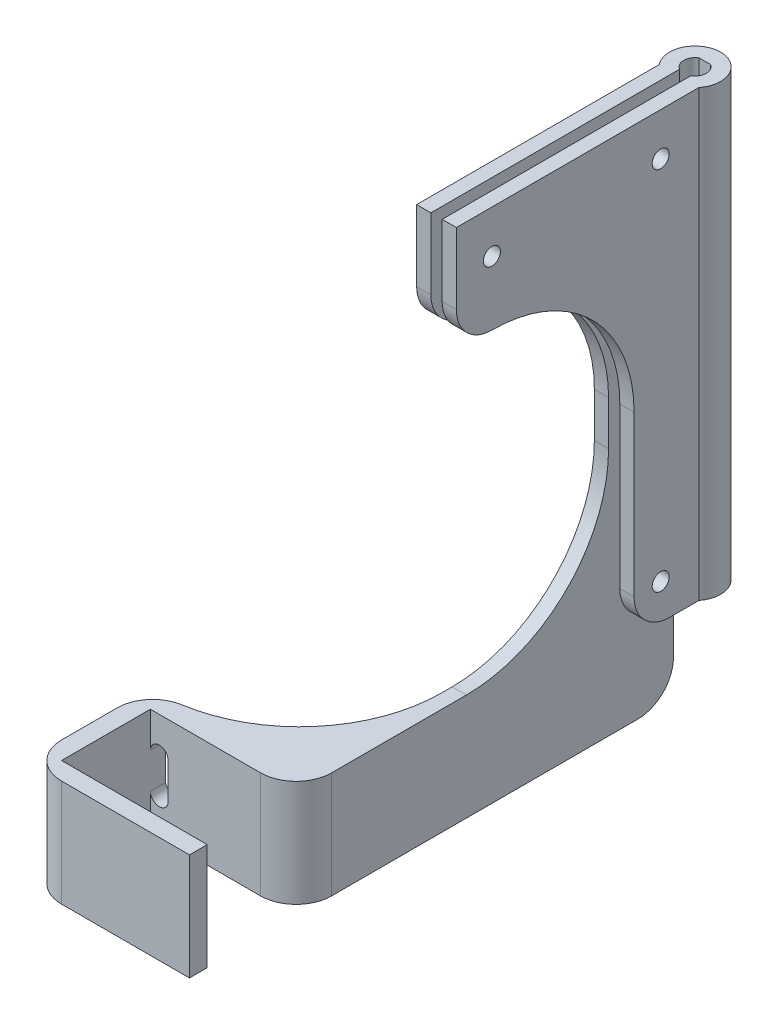
SolidWorks part; units mm, degrees
ref_plane "Front Plane" through (0, 0, 0) normal (0, 0, 1) x (1, 0, 0)
ref_plane "Top Plane" through (0, 0, 0) normal (0, 1, 0) x (1, 0, 0)
ref_plane "Right Plane" through (0, 0, 0) normal (1, 0, 0) x (0, 0, -1)
sketch "Sketch1" plane through (0, 0, 0) normal (0, 1, 0) x (1, 0, 0)
  line L0 (-1.5875, -2.7496) -> (-1.5875, -22.7496)
  line L1 (1.5875, -2.7496) -> (1.5875, -22.7496)
  line L2 (1.5875, 2.7496) -> (-1.5875, 2.7496)
  line L3 (5.5875, -4.5012) -> (5.5875, -22.7496)
  line L4 (-5.5875, -4.5012) -> (-5.5875, -22.7496)
  line L5 (-5.5875, -22.7496) -> (-1.5875, -22.7496)
  line L6 (1.5875, -22.7496) -> (5.5875, -22.7496)
  arc A0 (1.5875, -2.7496) -> (1.5875, 2.7496) centre (0, 0) ccw
  arc A1 (5.5875, -4.5012) -> (-5.5875, -4.5012) centre (0, 0) ccw
  arc A2 (-1.5875, 2.7496) -> (-1.5875, -2.7496) centre (0, 0) ccw
  arc A4 (1.5875, -2.7496) -> (-1.5875, -2.7496) centre (0, 0) ccw construction
  dimension "D1" = 3.175
  dimension "D2" = 20
  dimension "D3" = 3.175
  dimension "D5" = 3.175
  dimension "D4" = 4
extrude "Boss-Extrude1" add sketch "Sketch1" along normal blind 125
sketch "Sketch5" plane through (0, 125, 0) normal (0, 1, 0) x (1, 0, 0)
  line L1 (-1.5875, -110.675) -> (-1.5875, -105.675)
  line L2 (-47.5875, -105.675) -> (-47.5875, -140.675)
  line L3 (-47.5875, -140.675) -> (-1.5875, -140.675)
  line L4 (-1.5875, -140.675) -> (-1.5875, -135.675)
  line L5 (-1.5875, -135.675) -> (-42.5875, -135.675)
  line L9 (-1.5875, -22.7496) -> (-1.5875, -2.7496) construction
  line L10 (-42.5875, -110.675) -> (-1.5875, -110.675)
  line L12 (-42.5875, -135.675) -> (-42.5875, -110.675)
  line L13 (-47.5875, -105.675) -> (-1.5875, -105.675)
  line L18 (-18.6703, -3.175) -> (17.7565, -3.175) construction
  circle A0 centre (0, 0) radius 3.175 construction
  arc A1 (-1.5875, 2.7496) -> (-1.5875, -2.7496) centre (0, 0) ccw construction
  point P2 (-42.5875, -123.175)
  dimension "D2" = 120
  dimension "D1" = 41
  dimension "D3" = 25
  dimension "D4" = 5
  dimension "D5" = 5
  dimension "D7" = 5
extrude "Boss-Extrude2" add sketch "Sketch5" against normal mid plane 30 from offset 137.5 offset against normal yes
sketch "Sketch6" plane through (0, 125, 0) normal (0, 1, 0) x (1, 0, 0)
  line L0 (5.5875, -22.7496) -> (5.5875, -4.5012) construction
  line L1 (1.5875, -22.7496) -> (5.5875, -22.7496)
  line L2 (1.5875, -22.7496) -> (1.5875, -72.7496)
  line L3 (1.5875, -72.7496) -> (5.5875, -72.7496)
  line L4 (5.5875, -22.7496) -> (5.5875, -72.7496)
  line L6 (-1.5875, -22.7496) -> (-1.5875, -2.7496) construction
  line L7 (-5.5875, -22.7496) -> (-1.5875, -22.7496)
  line L8 (-5.5875, -22.7496) -> (-5.5875, -72.7496)
  line L9 (-5.5875, -72.7496) -> (-1.5875, -72.7496)
  line L10 (-1.5875, -22.7496) -> (-1.5875, -72.7496)
  dimension "D1" = 50
extrude "Boss-Extrude3" add sketch "Sketch6" against normal blind 30
hole_wizard "M4 Clearance Hole1" positions "Sketch2" profile "Sketch3" hole size "M4" standard "ANSI Metric" end condition through all
sketch "Sketch2" plane through (5.5875, 0, 0) normal (1, 0, 0) x (0, 0, -1)
  line L4 (-72.7496, 125) -> (-4.5012, 125) construction
  line L6 (-72.7496, 95) -> (-72.7496, 125) construction
  point P0 (-15.2496, 113)
  point P4 (-15.2496, 10)
  point P19 (-62.7496, 113)
  dimension "D1" = 103
  dimension "D2" = 12
  dimension "D3" = 47.5
  dimension "D4" = 10
sketch "Sketch3" plane through (5.5875, 113, 15.2496) normal (0, 1, 0) x (0, 0, -1)
  line L0 (0, 0) -> (0, 53.175)
  line L1 (0, 53.175) -> (2.4, 53.175)
  line L2 (2.4, 53.175) -> (2.4, 0)
  line L5 (2.4, 0) -> (0, 0)
  line L11 (0, -6.35) -> (0, 107.95) construction
  dimension "Thru Hole Dia." = 4.8
  dimension "Thru Hole Depth" = 53.175
sketch "Sketch9" plane through (-1.5875, 0, 0) normal (1, 0, 0) x (0, 0, -1)
  line L0 (-105.675, 2.5) -> (-22.7496, 2.5)
  line L1 (-105.675, 2.5) -> (-105.675, -27.5)
  line L2 (-105.675, -27.5) -> (-22.7496, -27.5)
  line L3 (-22.7496, 95) -> (-22.7496, 0) construction
  line L5 (-4.5012, 0) -> (-4.5012, -27.5)
  line L6 (-4.5012, -27.5) -> (-22.7496, -27.5)
  line L7 (-22.7496, 2.5) -> (-22.7496, 0)
  line L8 (-22.7496, 95) -> (-22.7496, 0) construction
  line L9 (-22.7496, 0) -> (-4.5012, 0) construction
  line L10 (-22.7496, 0) -> (-4.5012, 0)
extrude "Boss-Extrude5" add sketch "Sketch9" against normal up to surface (4 mm away) up to face at (-5.5875, 113, 12.8496)
chamfer "Chamfer2" [suppressed] distance 42 distance2 35
fillet "Fillet1" radius 40 4 edges at (3.5875, 95, 22.7496) (-3.5875, 95, 22.7496) (-3.5875, 2.5, 22.7496) (-5.5875, -12.5, 105.675)
fillet "Fillet2" radius 10 7 edges at (3.5875, 95, 72.7496) (-3.5875, 95, 72.7496) (3.5875, 0, 22.7496) (-1.5875, -12.5, 110.675) (-3.5875, -27.5, 4.5012) (-47.5875, -12.5, 140.675) (-47.5875, -12.5, 105.675)
ref_plane "Plane1" through (0, 0, 0) normal (-1, 0, 0) x (0, 0, 1)
ref_plane "Plane2" through (0, -15, 0) normal (0, 1, 0) x (1, 0, 0)
ref_axis "Axis1" through (0, -15, 105.5713) along (0, 0, -1)
sketch "Sketch11" [suppressed] plane through (0, 125, 0) normal (0, 1, 0) x (1, 0, 0)
  line L0 (-21.2191, -3.175) -> (29.064, -3.175) construction
  line L1 (5.5875, -65.675) -> (47.5875, -65.675)
  line L2 (5.5875, -72.7496) -> (5.5875, -4.5012) construction
  line L3 (47.5875, -65.675) -> (47.5875, -100.675)
  line L4 (47.5875, -100.675) -> (5.5875, -100.675)
  line L5 (5.5875, -100.675) -> (5.5875, -95.675)
  line L6 (5.5875, -95.675) -> (42.5875, -95.675)
  line L7 (42.5875, -95.675) -> (42.5875, -70.675)
  line L8 (42.5875, -70.675) -> (5.5875, -70.675)
  line L9 (5.5875, -70.675) -> (5.5875, -65.675)
  line L10 (1.5875, -2.7496) -> (1.5875, -72.7496) construction
  circle A0 centre (0, 0) radius 3.175 construction
  arc A1 (-1.5875, 2.7496) -> (-1.5875, -2.7496) centre (0, 0) ccw construction
  point P17 (42.5875, -83.175)
  dimension "D1" = 5
  dimension "D2" = 5
  dimension "D3" = 5
  dimension "D4" = 41
  dimension "D5" = 80
  dimension "D6" = 25
extrude "Boss-Extrude6" [suppressed] add sketch "Sketch11" along normal mid plane 30 from offset 137.5 offset against normal yes
sketch "Sketch13" [suppressed] plane through (5.5875, 0, 0) normal (-1, 0, 0) x (0, 0, 1)
  line L0 (70.675, 2.5) -> (22.7496, 2.5)
  line L1 (22.7496, 95) -> (22.7496, 0) construction
  line L2 (22.7496, 2.5) -> (22.7496, 0)
  line L3 (22.7496, 0) -> (4.5012, 0)
  line L4 (70.675, 2.5) -> (70.675, -27.5)
  line L5 (70.675, -27.5) -> (4.5012, -27.5)
  line L6 (4.5012, -27.5) -> (4.5012, 0)
extrude "Boss-Extrude8" [suppressed] add sketch "Sketch13" along normal up to surface (4 mm away) up to face at (1.5875, 113, 12.8496)
chamfer "Chamfer3" [suppressed] distance 42 distance2 35
fillet "Fillet5" [suppressed] radius 40
fillet "Fillet4" [suppressed] radius 10
sketch "Sketch14" plane through (0, 0, 110.675) normal (0, 0, 1) x (1, 0, 0)
  line L5 (-47.5875, -27.5) -> (-47.5875, 2.5) construction
  line L6 (-40.0875, -7.5) -> (-40.0875, -17.5) construction
  line L7 (-37.5875, -7.5) -> (-37.5875, -17.5)
  line L8 (-42.5875, -7.5) -> (-42.5875, -17.5)
  line L9 (-42.5875, -27.5) -> (-42.5875, 2.5) construction
  arc A0 (-37.5875, -7.5) -> (-42.5875, -7.5) centre (-40.0875, -7.5) ccw
  arc A1 (-42.5875, -17.5) -> (-37.5875, -17.5) centre (-40.0875, -17.5) ccw
  point P2 (-40.0875, -12.5)
  point P9 (-47.5875, -12.5)
  dimension "D1" = 5
  dimension "D2" = 10
extrude "Cut-Extrude1" cut sketch "Sketch14" against normal up to next
sketch "Sketch15" [suppressed] plane through (0, 0, 70.675) normal (0, 0, 1) x (1, 0, 0)
  line L0 (40.0875, -7.5) -> (40.0875, -17.5) construction
  line L1 (42.5875, -7.5) -> (42.5875, -17.5)
  line L2 (37.5875, -7.5) -> (37.5875, -17.5)
  line L3 (42.5875, 2.5) -> (42.5875, -27.5) construction
  arc A0 (42.5875, -7.5) -> (37.5875, -7.5) centre (40.0875, -7.5) ccw
  arc A1 (37.5875, -17.5) -> (42.5875, -17.5) centre (40.0875, -17.5) ccw
  point P2 (40.0875, -12.5)
  point P9 (42.5875, -12.5)
  dimension "D1" = 5
  dimension "D2" = 10
extrude "Cut-Extrude2" [suppressed] cut sketch "Sketch15" against normal up to next
